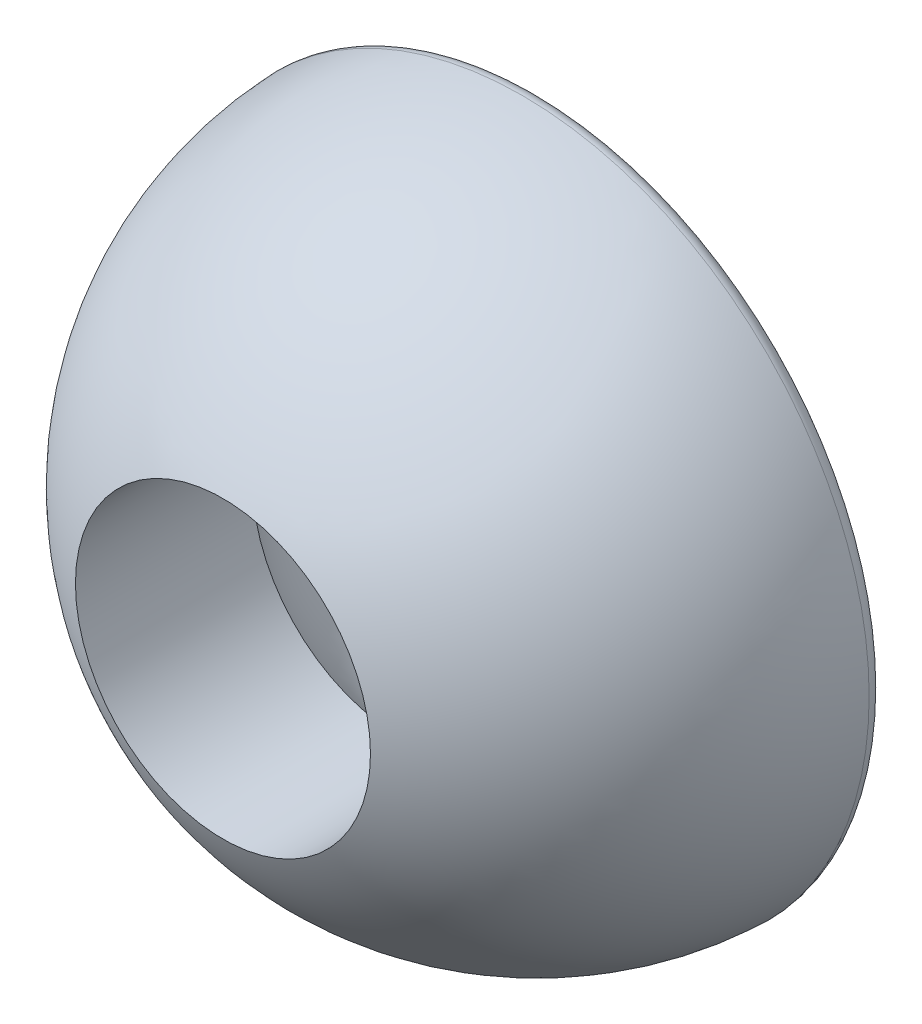
SolidWorks part; units mm, degrees
ref_plane "Front Plane" through (0, 0, 0) normal (0, 0, 1) x (1, 0, 0)
ref_plane "Top Plane" through (0, 0, 0) normal (0, 1, 0) x (1, 0, 0)
ref_plane "Right Plane" through (0, 0, 0) normal (1, 0, 0) x (0, 0, -1)
ref_axis "Polar Axis" through (0, 0, -14.3) along (0, 0, 1)
ref_axis "Solar Axis" through (-14.3, 0, 0) along (1, 0, 0)
sketch "Sketch2" plane through (0, 0, 0) normal (0, 1, 0) x (1, 0, 0)
  line L0 (5.6, 0) -> (9.65, 0)
  line L4 (4.1, -8.7357) -> (4.1, -3.8144)
  line L7 (0, 0) -> (0, -7) construction
  arc A0 (4.1, -3.8144) -> (5.6, 0) centre (0, 0) ccw
  arc A1 (4.1, -8.7357) -> (9.65, 0) centre (0, 0) ccw
  dimension "D1" = 7
  dimension "D2" = 4.1
  dimension "D3" = 5.6
  dimension "D4" = 19.3
revolve "Main Body" add sketch "Sketch2" angle 360 about L7
fillet "Bottom Fillet" radius 0.4 2 edges at (-9.65, 0, 0) (-5.6, 0, 0)
